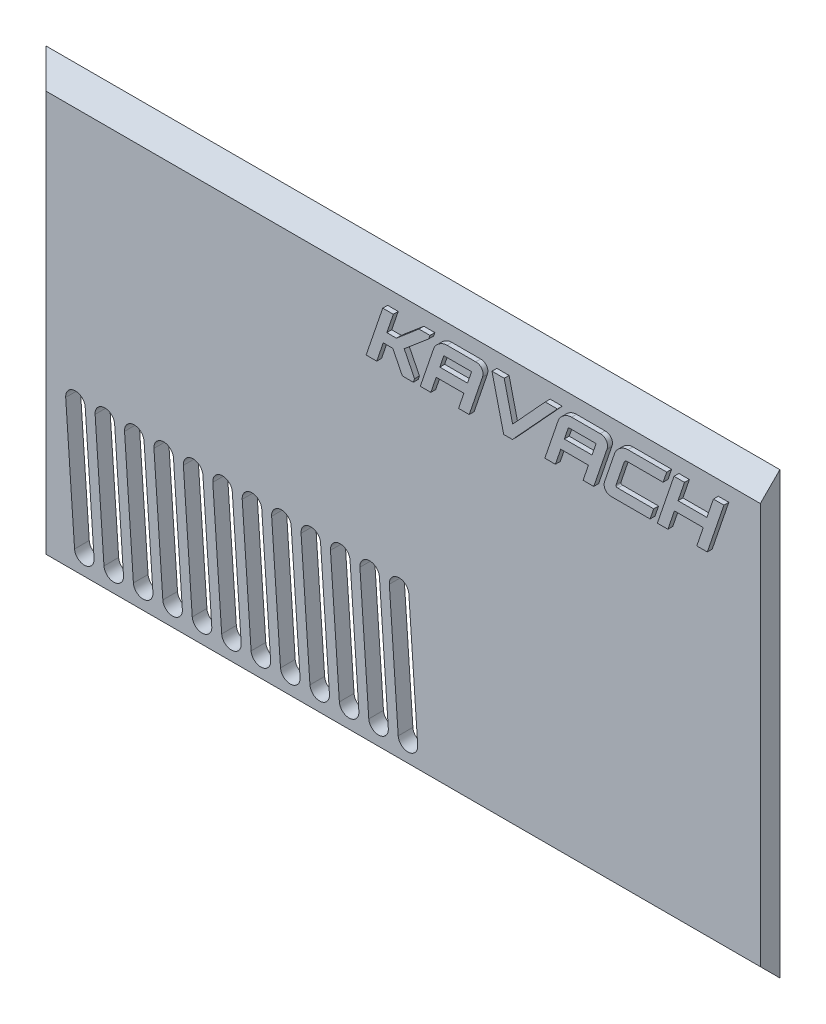
SolidWorks part; units mm, degrees
ref_plane "Front Plane" through (0, 0, 0) normal (0, 0, 1) x (1, 0, 0)
ref_plane "Top Plane" through (0, 0, 0) normal (0, 1, 0) x (1, 0, 0)
ref_plane "Right Plane" through (0, 0, 0) normal (1, 0, 0) x (0, 0, -1)
sketch "Sketch1" plane through (0, 0, 0) normal (0, 0, 1) x (1, 0, 0)
  line L0 (36.5, 22.5) -> (36.5, -22.5)
  line L5 (34.5, 20.5) -> (-36.5, 20.5) construction
  line L6 (-36.5, 20.5) -> (-36.5, -20.5) construction
  line L7 (-36.5, -20.5) -> (34.5, -20.5) construction
  line L8 (34.5, 20.5) -> (34.5, -20.5) construction
  line L10 (-38.5, -22.5) -> (36.5, -22.5)
  line L11 (36.5, -22.5) -> (36.5, -20.5)
  line L12 (36.5, -20.5) -> (31.77, -20.5)
  line L13 (31.77, -20.5) -> (-36.5, -20.5)
  line L14 (-36.5, -20.5) -> (-36.5, 20.5)
  line L15 (-36.5, 20.5) -> (31.77, 20.5)
  line L16 (31.77, 20.5) -> (36.5, 20.5)
  line L17 (36.5, 20.5) -> (36.5, 22.5)
  line L18 (36.5, 22.5) -> (-38.5, 22.5)
  line L19 (-38.5, 22.5) -> (-38.5, -22.5)
  line L20 (-38.5, -22.5) -> (36.5, -22.5)
  line L28 (36.5, 22.5) -> (-38.5, 22.5)
  line L29 (-38.5, 22.5) -> (-38.5, -22.5)
  dimension "D1" = 0
  dimension "D2" = 2
extrude "Boss-Extrude1" add sketch "Sketch1" along normal up to surface (2 mm away)
chamfer "Chamfer1" distance 2 angle 45 3 edges at (-1, -22.5, 2) (-38.5, 0, 2) (-1, 22.5, 2)
sketch "Sketch4" plane through (0, 0, 0) normal (0, 0, -1) x (-1, 0, 0)
  line L0 (-36.5, -22.5) -> (-36.5, 22.5) construction
  line L1 (-24.5, 20.25) -> (-22.25, 20.25)
  line L2 (-24.5, 20.25) -> (-24.5, 17)
  line L3 (-24.5, 17) -> (-22.25, 17)
  line L4 (-22.25, 20.25) -> (-22.25, 17)
  line L5 (-24.5, 20.25) -> (-22.25, 17) construction
  line L6 (-24.5, 17) -> (-22.25, 20.25) construction
  line L7 (-24.5, -17.25) -> (-22.25, -17.25)
  line L8 (-24.5, -17.25) -> (-24.5, -20.5)
  line L9 (-24.5, -20.5) -> (-22.25, -20.5)
  line L10 (-22.25, -17.25) -> (-22.25, -20.5)
  line L11 (-24.5, -17.25) -> (-22.25, -20.5) construction
  line L12 (-24.5, -20.5) -> (-22.25, -17.25) construction
  line L13 (33, 1.125) -> (36.25, 1.125)
  line L14 (33, 1.125) -> (33, -1.125)
  line L15 (33, -1.125) -> (36.25, -1.125)
  line L16 (36.25, 1.125) -> (36.25, -1.125)
  line L17 (33, 1.125) -> (36.25, -1.125) construction
  line L18 (33, -1.125) -> (36.25, 1.125) construction
  line L22 (-36.5, 22.5) -> (38.5, 22.5) construction
  line L23 (38.5, -22.5) -> (-36.5, -22.5) construction
  line L24 (38.5, 22.5) -> (38.5, -22.5) construction
  point P0 (-23.375, 18.625)
  point P5 (-23.375, -18.875)
  point P10 (34.625, 0)
  point P33 (38.5, 0)
  dimension "D1" = 3.25
  dimension "D2" = 2.25
  dimension "D3" = 3.25
  dimension "D4" = 2.25
  dimension "D5" = 3.25
  dimension "D6" = 2.25
  dimension "D7" = 12
  dimension "D8" = 2.25
  dimension "D9" = 2
  dimension "D10" = 2.25
extrude "Cut-Extrude1" cut sketch "Sketch4" against normal blind 1.5
shell "Shell1" thickness 1.5 removed face at (23.375, 18.625, 0)
sketch "Sketch5" plane through (0, 0, 0) normal (0, 0, -1) x (-1, 0, 0)
  line L0 (33.5024, -5.5317) -> (32.5956, -18.5) construction
  line L1 (34.5, -5.6014) -> (33.5932, -18.5698)
  line L2 (32.5049, -5.4619) -> (31.598, -18.4302)
  line L3 (36.5, -20.5) -> (-34.5, -20.5) construction
  line L5 (30.4951, -5.5317) -> (29.5883, -18.5) construction
  line L6 (31.4927, -5.6014) -> (30.5858, -18.5698)
  line L7 (29.4975, -5.4619) -> (28.5907, -18.4302)
  line L8 (27.4878, -5.5317) -> (26.581, -18.5) construction
  line L9 (28.4853, -5.6014) -> (27.5785, -18.5698)
  line L10 (26.4902, -5.4619) -> (25.5834, -18.4302)
  line L11 (24.4805, -5.5317) -> (23.5736, -18.5) construction
  line L12 (25.478, -5.6014) -> (24.5712, -18.5698)
  line L13 (23.4829, -5.4619) -> (22.5761, -18.4302)
  line L14 (21.4731, -5.5317) -> (20.5663, -18.5) construction
  line L15 (22.4707, -5.6014) -> (21.5639, -18.5698)
  line L16 (20.4756, -5.4619) -> (19.5687, -18.4302)
  line L17 (18.4658, -5.5317) -> (17.559, -18.5) construction
  line L18 (19.4634, -5.6014) -> (18.5565, -18.5698)
  line L19 (17.4682, -5.4619) -> (16.5614, -18.4302)
  line L20 (15.4585, -5.5317) -> (14.5516, -18.5) construction
  line L21 (16.456, -5.6014) -> (15.5492, -18.5698)
  line L22 (14.4609, -5.4619) -> (13.5541, -18.4302)
  line L23 (12.4512, -5.5317) -> (11.5443, -18.5) construction
  line L24 (13.4487, -5.6014) -> (12.5419, -18.5698)
  line L25 (11.4536, -5.4619) -> (10.5468, -18.4302)
  line L26 (9.4438, -5.5317) -> (8.537, -18.5) construction
  line L27 (10.4414, -5.6014) -> (9.5346, -18.5698)
  line L28 (8.4463, -5.4619) -> (7.5394, -18.4302)
  line L29 (6.4365, -5.5317) -> (5.5297, -18.5) construction
  line L30 (7.4341, -5.6014) -> (6.5272, -18.5698)
  line L31 (5.4389, -5.4619) -> (4.5321, -18.4302)
  line L32 (3.4292, -5.5317) -> (2.5223, -18.5) construction
  line L33 (4.4267, -5.6014) -> (3.5199, -18.5698)
  line L34 (2.4316, -5.4619) -> (1.5248, -18.4302)
  line L35 (0.4219, -5.5317) -> (-0.485, -18.5) construction
  line L36 (1.4194, -5.6014) -> (0.5126, -18.5698)
  line L37 (-0.5757, -5.4619) -> (-1.4825, -18.4302)
  line L39 (36.5, 20.5) -> (36.5, -20.5) construction
  arc A0 (34.5, -5.6014) -> (32.5049, -5.4619) centre (33.5024, -5.5317) ccw
  arc A1 (31.598, -18.4302) -> (33.5932, -18.5698) centre (32.5956, -18.5) ccw
  arc A2 (31.4927, -5.6014) -> (29.4975, -5.4619) centre (30.4951, -5.5317) ccw
  arc A3 (28.5907, -18.4302) -> (30.5858, -18.5698) centre (29.5883, -18.5) ccw
  arc A4 (28.4853, -5.6014) -> (26.4902, -5.4619) centre (27.4878, -5.5317) ccw
  arc A5 (25.5834, -18.4302) -> (27.5785, -18.5698) centre (26.581, -18.5) ccw
  arc A6 (25.478, -5.6014) -> (23.4829, -5.4619) centre (24.4805, -5.5317) ccw
  arc A7 (22.5761, -18.4302) -> (24.5712, -18.5698) centre (23.5736, -18.5) ccw
  arc A8 (22.4707, -5.6014) -> (20.4756, -5.4619) centre (21.4731, -5.5317) ccw
  arc A9 (19.5687, -18.4302) -> (21.5639, -18.5698) centre (20.5663, -18.5) ccw
  arc A10 (19.4634, -5.6014) -> (17.4682, -5.4619) centre (18.4658, -5.5317) ccw
  arc A11 (16.5614, -18.4302) -> (18.5565, -18.5698) centre (17.559, -18.5) ccw
  arc A12 (16.456, -5.6014) -> (14.4609, -5.4619) centre (15.4585, -5.5317) ccw
  arc A13 (13.5541, -18.4302) -> (15.5492, -18.5698) centre (14.5516, -18.5) ccw
  arc A14 (13.4487, -5.6014) -> (11.4536, -5.4619) centre (12.4512, -5.5317) ccw
  arc A15 (10.5468, -18.4302) -> (12.5419, -18.5698) centre (11.5443, -18.5) ccw
  arc A16 (10.4414, -5.6014) -> (8.4463, -5.4619) centre (9.4438, -5.5317) ccw
  arc A17 (7.5394, -18.4302) -> (9.5346, -18.5698) centre (8.537, -18.5) ccw
  arc A18 (7.4341, -5.6014) -> (5.4389, -5.4619) centre (6.4365, -5.5317) ccw
  arc A19 (4.5321, -18.4302) -> (6.5272, -18.5698) centre (5.5297, -18.5) ccw
  arc A20 (4.4267, -5.6014) -> (2.4316, -5.4619) centre (3.4292, -5.5317) ccw
  arc A21 (1.5248, -18.4302) -> (3.5199, -18.5698) centre (2.5223, -18.5) ccw
  arc A22 (1.4194, -5.6014) -> (-0.5757, -5.4619) centre (0.4219, -5.5317) ccw
  arc A23 (-1.4825, -18.4302) -> (0.5126, -18.5698) centre (-0.485, -18.5) ccw
  point P2 (33.049, -12.0158)
  point P12 (30.0417, -12.0158)
  point P22 (27.0344, -12.0158)
  point P29 (24.027, -12.0158)
  point P36 (21.0197, -12.0158)
  point P43 (18.0124, -12.0158)
  point P50 (15.0051, -12.0158)
  point P57 (11.9977, -12.0158)
  point P64 (8.9904, -12.0158)
  point P71 (5.9831, -12.0158)
  point P76 (2.9758, -12.0158)
  point P83 (-0.0316, -12.0158)
  dimension "D7" = 2
  dimension "D1" = 2
  dimension "D2" = 13
  dimension "D3" = 12
  dimension "D4" = 86
  dimension "D5" = 1
  dimension "D6" = 2
extrude "Cut-Extrude2" cut sketch "Sketch5" against normal up to next
sketch "Sketch6" plane through (0, 0, 2) normal (0, 0, 1) x (1, 0, 0)
  line L0 (-3.6864, 14) -> (36.5, 14) construction
  line L2 (36.5, 20.5) -> (36.5, -20.5) construction
  line L5 (36.5, 20.5) -> (-36.5, 20.5) construction
  text T0 "<b><i>KAVACH </i></b>" font "Orbitron Black" height 5
  dimension "D1" = 6.5
extrude "Boss-Extrude2" add sketch "Sketch6" along normal blind 0.5
sketch "Sketch7" plane through (0, 0, 2) normal (0, 0, 1) x (1, 0, 0)
  line L0 (-5.9697, 10.5) -> (36.5, 10.5) construction
  line L388 (-5.9697, 7.5) -> (36.5, 7.5) construction
  line L390 (-5.9697, 4.5) -> (36.5, 4.5) construction
  line L392 (36.5, 20.5) -> (36.5, -20.5) construction
  line L393 (-3.6864, 14) -> (36.5, 14) construction
  text T0 "<b>Kinetic Anti-UAV </b>" font "Orbitron Black" height 1.75
  text T1 "<b>Automated Combat </b>" font "Orbitron Black" height 1.5
  text T2 "<b>Hardware</b>" font "Orbitron Black" height 1.5
  dimension "D1" = 3.5
  dimension "D2" = 3
  dimension "D3" = 3
extrude "Boss-Extrude3" [suppressed] add sketch "Sketch7" along normal blind 0.5
equation "\"D3@Sketch4\"=\"D1@Sketch4\""
equation "\"D4@Sketch4\"=\"D2@Sketch4\""
equation "\"D5@Sketch4\"=\"D1@Sketch4\""
equation "\"D6@Sketch4\"=\"D2@Sketch4\""
equation "\"D10@Sketch4\"=\"D8@Sketch4\""
equation "\"D3@Sketch7\"=\"D2@Sketch7\""
